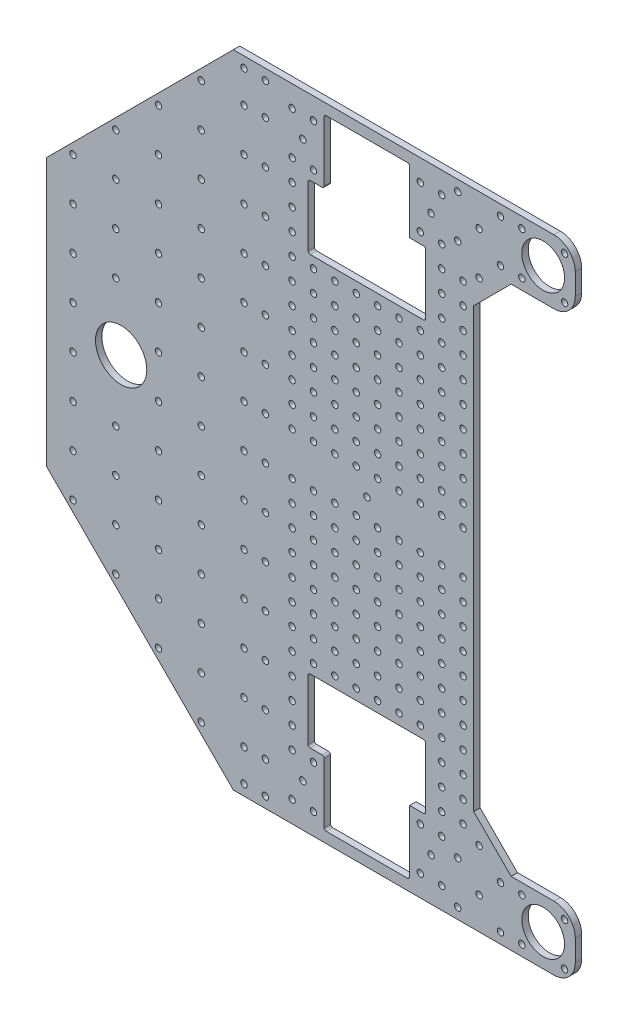
SolidWorks part; units mm, degrees
ref_plane "Front Plane" through (0, 0, 0) normal (0, 0, 1) x (1, 0, 0)
ref_plane "Top Plane" through (0, 0, 0) normal (0, 1, 0) x (1, 0, 0)
ref_plane "Right Plane" through (0, 0, 0) normal (1, 0, 0) x (0, 0, -1)
ref_axis "Axis1" through (-88.99, 0, 0) along (1, 0, 0)
ref_axis "Axis3" through (0, -55, 0) along (0, 1, 0)
sketch "Sketch1" plane through (0, 0, 0) normal (0, 0, 1) x (1, 0, 0)
  line L0 (-150, 62.5) -> (-150, -62.5)
  line L1 (-150, -62.5) -> (-62.5, -150)
  line L2 (-62.5, -150) -> (87.5, -150)
  line L3 (97.5, -140) -> (97.5, -130)
  line L4 (87.5, -120) -> (67.5, -120)
  line L5 (-20, 100) -> (20, -100) construction
  line L6 (-20, 100) -> (20, 100) construction
  line L7 (97.5, 130) -> (97.5, 140)
  line L8 (87.5, 150) -> (-62.5, 150)
  line L9 (-62.5, 150) -> (-150, 62.5)
  line L10 (-88.99, 0) -> (88.99, 0) construction
  line L12 (0, -55) -> (0, 55) construction
  line L13 (50, 102.5) -> (50, -102.5)
  line L14 (-20, 100) -> (-20, -100) construction
  line L15 (50, 102.5) -> (67.5, 120)
  line L16 (67.5, 120) -> (87.5, 120)
  line L17 (67.5, -120) -> (50, -102.5)
  line L18 (-20, -100) -> (20, -100) construction
  line L19 (20, 100) -> (20, -100) construction
  line L20 (20, 100) -> (-20, -100) construction
  line L23 (-62.5, -150) -> (-52.5, -150) construction
  circle A0 centre (105.5, 0) radius 38 construction
  circle A1 centre (105.5, -76) radius 38 construction
  circle A2 centre (105.5, 76) radius 38 construction
  arc A3 (97.5, 130) -> (87.5, 120) centre (87.5, 130) cw
  arc A4 (97.5, -140) -> (87.5, -150) centre (87.5, -140) cw
  arc A5 (87.5, -120) -> (97.5, -130) centre (87.5, -130) cw
  arc A6 (87.5, 150) -> (97.5, 140) centre (87.5, 140) cw
  circle A7 centre (0, 0) radius 162.5 construction
  circle A10 centre (0, 0) radius 1.5
  point P2 (-150, 0)
  point P6 (0, 0)
  point P14 (-41.3479, 0)
  point P28 (0, 0)
  point P30 (0, 0)
  point P34 (97.5, 120)
  point P38 (97.5, -150)
  point P43 (97.5, 150)
  dimension "D15" = 76
  dimension "D8" = 10
  dimension "D13" = 10
  dimension "D19" = 10
  dimension "D20" = 10
  dimension "D30" = 3
  dimension "D1" = 125
  dimension "D2" = 160
  dimension "D3" = 135
  dimension "D4" = 150
  dimension "D5" = 30
  dimension "D6" = 150
  dimension "D7" = 135
  dimension "D9" = 160
  dimension "D10" = 30
  dimension "D11" = 50
  dimension "D12" = 87.5
  dimension "D14" = 300
  dimension "D16" = 123.7437
  dimension "D17" = 300
  dimension "D18" = 205
  dimension "D21" = 200
  dimension "D22" = 40
extrude "Main" add sketch "Sketch1" along normal blind 3
sketch "Sketch10" plane through (0, 0, 3) normal (0, 0, 1) x (1, 0, 0)
  line L0 (57.5, 140) -> (57.5, 150) construction
  line L1 (-62.5, 150) -> (-52.5, 150) construction
  line L2 (-62.5, 150) -> (-52.5, 140) construction
  line L3 (-62.5, 140) -> (-52.5, 150) construction
  line L4 (-62.5, 150) -> (-62.5, 140) construction
  line L5 (-62.5, 140) -> (-52.5, 140) construction
  line L6 (-52.5, 150) -> (-52.5, 140) construction
  line L7 (87.5, 150) -> (-62.5, 150) construction
  line L8 (57.5, 140) -> (67.5, 140) construction
  line L9 (97.5, 130) -> (97.5, 140) construction
  line L11 (-42.5, 140) -> (-52.5, 140) construction
  line L12 (-42.5, 140) -> (-52.5, 150) construction
  line L13 (-42.5, 150) -> (-52.5, 140) construction
  line L14 (-42.5, 140) -> (-42.5, 150) construction
  line L15 (-42.5, 150) -> (-52.5, 150) construction
  line L16 (-52.5, 140) -> (-52.5, 150) construction
  line L18 (57.5, 150) -> (67.5, 150) construction
  line L19 (67.5, 140) -> (67.5, 150) construction
  circle A1 centre (-57.5, 145) radius 1.5
  circle A10 centre (-47.5, 145) radius 1.5
  circle A12 centre (62.5, 145) radius 1.5
  circle A13 centre (62.5, 125) radius 1.5
  circle A14 centre (42.5, 145) radius 1.5
  circle A15 centre (42.5, 125) radius 1.5
  circle A17 centre (52.5, 135) radius 1.5
  circle A18 centre (52.5, 115) radius 1.5
  point P0 (62.5, 140)
  point P9 (57.5, 145)
  point P49 (67.5, 145)
  point P52 (62.5, 150)
  dimension "D2" = 3
  dimension "D5" = 3
  dimension "D14" = 3
  dimension "D17" = 3
  dimension "D24" = 3
  dimension "D3" = 10
  dimension "D4" = 10
  dimension "D6" = 100
  dimension "D7" = 10
  dimension "D8" = 10
  dimension "D9" = 40
  dimension "D18" = 20
  dimension "D19" = 20
  dimension "D23" = 20
  dimension "D25" = 10
  dimension "D26" = 10
extrude "MainHoles" cut sketch "Sketch10" against normal through all
sketch "Sketch2" plane through (0, 0, 3) normal (0, 0, 1) x (1, 0, 0)
  line L0 (-27.5, 115) -> (-27.5, 85)
  line L1 (-27.5, 85) -> (27.5, 85)
  line L2 (27.5, 85) -> (27.5, 115)
  line L3 (27.5, 115) -> (20, 115)
  line L4 (20, 115) -> (20, 145)
  line L5 (20, 145) -> (-20, 145)
  line L6 (-20, 145) -> (-20, 115)
  line L7 (-20, 115) -> (-27.5, 115)
  line L9 (-88.99, 0) -> (88.99, 0) construction
  line L10 (87.5, 150) -> (-62.5, 150) construction
  line L11 (0, -55) -> (0, 55) construction
  point P9 (0, 85)
  dimension "D1" = 55
  dimension "D2" = 85
  dimension "D3" = 40
  dimension "D4" = 30
  dimension "D5" = 30
  dimension "D6" = 5
extrude "MotorCoderLeftHole" cut sketch "Sketch2" against normal through all
sketch "Sketch8" plane through (0, 0, 3) normal (0, 0, 1) x (1, 0, 0)
  line L1 (-35, 140) -> (-25, 120) construction
  line L2 (-25, 140) -> (-35, 120) construction
  line L3 (0, -55) -> (0, 55) construction
  line L4 (-39, 140.7238) -> (-39, 119.2762) construction
  line L5 (-21, 119.2762) -> (-21, 140.7238) construction
  line L6 (-39, 130) -> (-21, 130) construction
  line L7 (-20, 145) -> (-20, 115) construction
  line L8 (87.5, 150) -> (-62.5, 150) construction
  circle A0 centre (-30, 130) radius 1.5
  circle A1 centre (-35, 120) radius 1.5
  circle A2 centre (-25, 120) radius 1.5
  circle A3 centre (-35, 140) radius 1.5
  circle A4 centre (-25, 140) radius 1.5
  arc A5 (-39, 119.2762) -> (-21, 119.2762) centre (-30, 130) ccw construction
  arc A6 (-21, 140.7238) -> (-39, 140.7238) centre (-30, 130) ccw construction
  circle A7 centre (-47.5, 145) radius 1.5 construction
  point P0 (-20, 130)
  point P20 (-30, 130)
  point P24 (-30, 144)
  point P25 (-30, 116)
  dimension "D1" = 3
  dimension "D6" = 3
  dimension "D7" = 14
  dimension "D2" = 20
  dimension "D3" = 10
  dimension "D4" = 20
  dimension "D5" = 30
  dimension "D8" = 28
  dimension "D9" = 18
  dimension "D10" = 12.5
extrude "LinearBallFixLeft" cut sketch "Sketch8" against normal through all
mirror "LinearBallFixLeftMirror" about plane through (0, 0, 0) normal (1, 0, 0) of "LinearBallFixLeft"
fillet "Fillet1" radius 1 7 edges at (-20, 145, 1.5) (27.5, 115, 1.5) (20, 145, 1.5) (-20, 115, 1.5) (-27.5, 115, 1.5) (27.5, 85, 1.5) (-27.5, 85, 1.5)
sketch "Sketch4" plane through (0, 0, 3) normal (0, 0, 1) x (1, 0, 0)
  line L0 (-88.99, 0) -> (88.99, 0) construction
  line L2 (0, -55) -> (0, 55) construction
  circle A0 centre (-57.5, 10) radius 1.5
  dimension "D1" = 3
  dimension "D2" = 57.5
  dimension "D3" = 10
extrude "BottomLeftHole" cut sketch "Sketch4" against normal through all
pattern_linear "LPattern1" count 5 spacing 20 along (-1, 0, 0) of "BottomLeftHole"
sketch "Sketch9" plane through (0, 0, 3) normal (0, 0, 1) x (1, 0, 0)
  line L0 (-88.99, 0) -> (88.99, 0) construction
  circle A0 centre (-47.5, 10) radius 1.5
  dimension "D1" = 3
  dimension "D2" = 15
  dimension "D3" = 10
extrude "Cut-Extrude1" cut sketch "Sketch9" against normal through all
pattern_linear "BottomLeftHoleLPattern" count 7 spacing 20 along (0, 1, 0) of "LPattern1", "Cut-Extrude1"
sketch "Sketch7" plane through (0, 0, 3) normal (0, 0, 1) x (1, 0, 0)
  line L0 (-88.99, 0) -> (88.99, 0) construction
  line L1 (0, -55) -> (0, 55) construction
  circle A0 centre (-5, 10) radius 1.5
  circle A1 centre (-15, 10) radius 1.5
  circle A2 centre (5, 10) radius 1.5
  circle A3 centre (-25, 10) radius 1.5
  circle A4 centre (15, 10) radius 1.5
  circle A5 centre (-35, 10) radius 1.5
  circle A6 centre (25, 10) radius 1.5
  circle A7 centre (45, 10) radius 1.5
  circle A9 centre (35, 10) radius 1.5
  point P22 (45, 10)
  point P23 (0, 0)
  dimension "D1" = 3
  dimension "D10" = 10
  dimension "D11" = 3
  dimension "D2" = 10
  dimension "D3" = 10
  dimension "D4" = 10
  dimension "D5" = 10
  dimension "D6" = 10
  dimension "D7" = 10
  dimension "D8" = 10
  dimension "D9" = 5
  dimension "D12" = 10
extrude "MotorFixHoles" cut sketch "Sketch7" against normal through all
pattern_linear "MotorFixHoleLPattern" count 11 spacing 10 along (0, 1, 0) of "MotorFixHoles"
sketch "Sketch3" plane through (0, 0, 3) normal (0, 0, 1) x (1, 0, 0)
  line L0 (-88.99, 0) -> (88.99, 0) construction
  line L1 (-150, 62.5) -> (-150, -62.5) construction
  line L2 (82.5, 135) -> (82.5, -135) construction
  line L3 (97.5, 130) -> (97.5, 140) construction
  line L5 (87.5, 150) -> (-62.5, 150) construction
  circle A0 centre (-115, 0) radius 12
  circle A1 centre (82.5, 135) radius 10
  circle A2 centre (82.5, -135) radius 10
  point P10 (45, 0)
  point P26 (82.5, 0)
  dimension "D1" = 24
  dimension "D3" = 20
  dimension "D2" = 35
  dimension "D4" = 15
  dimension "D5" = 15
extrude "BigHoles" cut sketch "Sketch3" against normal through all
sketch "Sketch5" plane through (0, 0, 3) normal (0, 0, 1) x (1, 0, 0)
  line L1 (97.5, 130) -> (97.5, 140) construction
  line L2 (87.5, 150) -> (-62.5, 150) construction
  circle A1 centre (72.5, 125) radius 1.5
  circle A2 centre (92.5, 125) radius 1.5
  circle A3 centre (72.5, 145) radius 1.5
  circle A4 centre (92.5, 145) radius 1.5
  circle A5 centre (62.5, 145) radius 1.5 construction
  dimension "D3" = 20
  dimension "D5" = 10
  dimension "D8" = 5
  dimension "D9" = 3
  dimension "D1" = 20
  dimension "D2" = 5
  dimension "D4" = 20
extrude "FrontBallsFix" cut sketch "Sketch5" against normal through all
mirror "Mirror2" about plane through (0, 0, 0) normal (0, 1, 0) of "Fillet1", "Cut-Extrude1", "LinearBallFixLeftMirror", "BottomLeftHole", "BottomLeftHoleLPattern", "LinearBallFixLeft", "MotorCoderLeftHole", "LPattern1", "MotorFixHoles", "MotorFixHoleLPattern", "FrontBallsFix", "BigHoles", "MainHoles"
